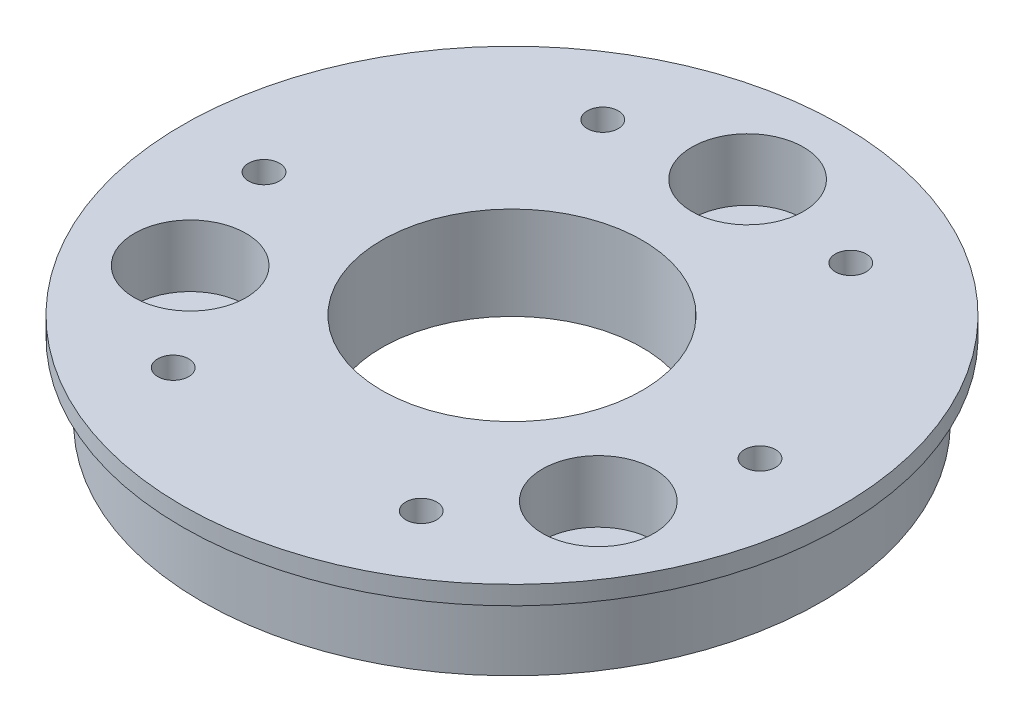
SolidWorks part; units mm, degrees
ref_plane "Front Plane" through (0, 0, 0) normal (0, 0, 1) x (1, 0, 0)
ref_plane "Top Plane" through (0, 0, 0) normal (0, 1, 0) x (1, 0, 0)
ref_plane "Right Plane" through (0, 0, 0) normal (1, 0, 0) x (0, 0, -1)
sketch "Sketch1" plane through (0, 0, 0) normal (0, 1, 0) x (1, 0, 0)
  circle A0 centre (0, 0) radius 25
  dimension "D1" = 50
extrude "Boss-Extrude1" add sketch "Sketch1" along normal blind 6
sketch "Sketch2" plane through (0, 6, 0) normal (0, 1, 0) x (1, 0, 0)
  circle A0 centre (0, 0) radius 10.5
  dimension "D1" = 21
extrude "Cut-Extrude1" cut sketch "Sketch2" against normal up to next
sketch "Sketch3" plane through (0, 6, 0) normal (0, 1, 0) x (1, 0, 0)
  circle A0 centre (0, 0) radius 19 construction
  circle A1 centre (0, 19) radius 2.5
  circle A2 centre (16.4545, 9.5) radius 2.5
  circle A3 centre (16.4545, -9.5) radius 2.5
  circle A4 centre (0, -19) radius 2.5
  circle A5 centre (-16.4545, -9.5) radius 2.5
  circle A6 centre (-16.4545, 9.5) radius 2.5
  point P17 (0, 0)
  dimension "D1" = 38
  dimension "D2" = 5
  dimension "D3" = 6
extrude "Cut-Extrude2" cut sketch "Sketch3" against normal through all
ref_axis "Axis1" through (0, 0, 0) along (0, 1, 0)
sketch "Sketch5" plane through (0, 6, 0) normal (0, 1, 0) x (1, 0, 0)
  circle A0 centre (0, 0) radius 20 construction
  circle A1 centre (20, 0) radius 1.25
  circle A2 centre (10, -17.3205) radius 1.25
  circle A3 centre (-10, -17.3205) radius 1.25
  circle A4 centre (-20, 0) radius 1.25
  circle A5 centre (-10, 17.3205) radius 1.25
  circle A6 centre (10, 17.3205) radius 1.25
  point P18 (0, 0)
  dimension "D1" = 40
  dimension "D2" = 2.5
  dimension "D3" = 6
extrude "Cut-Extrude3" cut sketch "Sketch5" against normal blind 4
sketch "Sketch6" plane through (0, 6, 0) normal (0, 1, 0) x (1, 0, 0)
  circle A0 centre (0, 0) radius 26.5767
  circle A1 centre (0, 0) radius 10.5 construction
  circle A2 centre (0, 0) radius 10.5
  circle A3 centre (10, -17.3205) radius 1.25 construction
  circle A4 centre (10, -17.3205) radius 1.25
  circle A5 centre (-10, -17.3205) radius 1.25 construction
  circle A6 centre (-10, -17.3205) radius 1.25
  circle A7 centre (-20, 0) radius 1.25 construction
  circle A8 centre (-10, 17.3205) radius 1.25 construction
  circle A9 centre (10, 17.3205) radius 1.25 construction
  circle A10 centre (20, 0) radius 1.25 construction
  circle A11 centre (-20, 0) radius 1.25
  circle A12 centre (-10, 17.3205) radius 1.25
  circle A13 centre (10, 17.3205) radius 1.25
  circle A14 centre (20, 0) radius 1.25
extrude "Boss-Extrude2" add sketch "Sketch6" along normal blind 1.5
sketch "Sketch7" plane through (0, 7.5, 0) normal (0, 1, 0) x (1, 0, 0)
  circle A0 centre (0, 19) radius 2.5 construction
  circle A1 centre (-16.4545, -9.5) radius 2.5 construction
  circle A2 centre (16.4545, -9.5) radius 2.5 construction
  circle A3 centre (0, 19) radius 2.5 construction
  circle A4 centre (-16.4545, -9.5) radius 2.5 construction
  circle A5 centre (16.4545, -9.5) radius 2.5 construction
  circle A6 centre (16.4545, -9.5) radius 4.5
  circle A7 centre (-16.4545, -9.5) radius 4.5
  circle A8 centre (0, 19) radius 4.5
  dimension "D1" = 9
extrude "Cut-Extrude4" cut sketch "Sketch7" against normal blind 5
sketch "Sketch8" plane through (0, 6, 0) normal (0, -1, 0) x (1, 0, 0)
  circle A0 centre (0, 19) radius 2.5 construction
  circle A1 centre (16.4545, -9.5) radius 2.5 construction
  circle A2 centre (0, 19) radius 2.5
  circle A3 centre (16.4545, -9.5) radius 2.5
  circle A5 centre (-16.4545, -9.5) radius 2.5
  circle A6 centre (-16.4545, -9.5) radius 2.5
  dimension "D1" = 0
extrude "Boss-Extrude3" add sketch "Sketch8" along normal blind 3
hole_wizard "M3x0.5 Tapped Hole1" positions "Sketch9" profile "Sketch10" tap size "M3x0.5" standard "ANSI Metric"
sketch "Sketch9" plane through (0, 7.5, 0) normal (0, 1, 0) x (1, 0, 0)
  point P0 (-10, 17.3205)
  point P3 (-20, 0)
  point P6 (-10, -17.3205)
  point P9 (10, 17.3205)
  point P12 (20, 0)
  point P15 (10, -17.3205)
cosmetic thread "Hole Thread1" parameters "D1"=4.6, "D2"=8.5
cosmetic thread "Hole Thread2" parameters "D1"=4.6, "D2"=8.5
cosmetic thread "Hole Thread3" parameters "D1"=4.6, "D2"=8.5
cosmetic thread "Hole Thread4" parameters "D1"=4.6, "D2"=8.5
cosmetic thread "Hole Thread5" parameters "D1"=4.6, "D2"=8.5
cosmetic thread "Hole Thread6" parameters "D1"=4.6, "D2"=8.5
sketch "Sketch10" plane through (-10, 7.5, -17.3205) normal (1, 0, 0) x (0, 0, 1)
  line L0 (0, 0) -> (0, 5.7511)
  line L1 (0, 5.7511) -> (1.25, 5)
  line L2 (1.25, 5) -> (1.25, 0)
  line L5 (1.25, 0) -> (0, 0)
  line L10 (0, 5.7511) -> (-1.25, 5) construction
  line L11 (0, -6.35) -> (0, 107.95) construction
  dimension "Tap Drill Dia." = 2.5
  dimension "Tap Drill Depth" = 5
  dimension "Drill Angle" = 118
equation "\"Output Pin Diameter\"= 38"
equation "\"D1@Sketch3\"=\"Output Pin Diameter\""
equation "\"Pin Diameter\"=5"
equation "\"D2@Sketch3\"=\"Pin Diameter\""
equation "\"Outer Diameter\"= 50"
equation "\"D1@Sketch1\"=\"Outer Diameter\""
equation "\"Inner Diameter\"= 21"
equation "\"D1@Sketch2\"=\"Inner Diameter\""
equation "\"Margin\"= 0.5"
